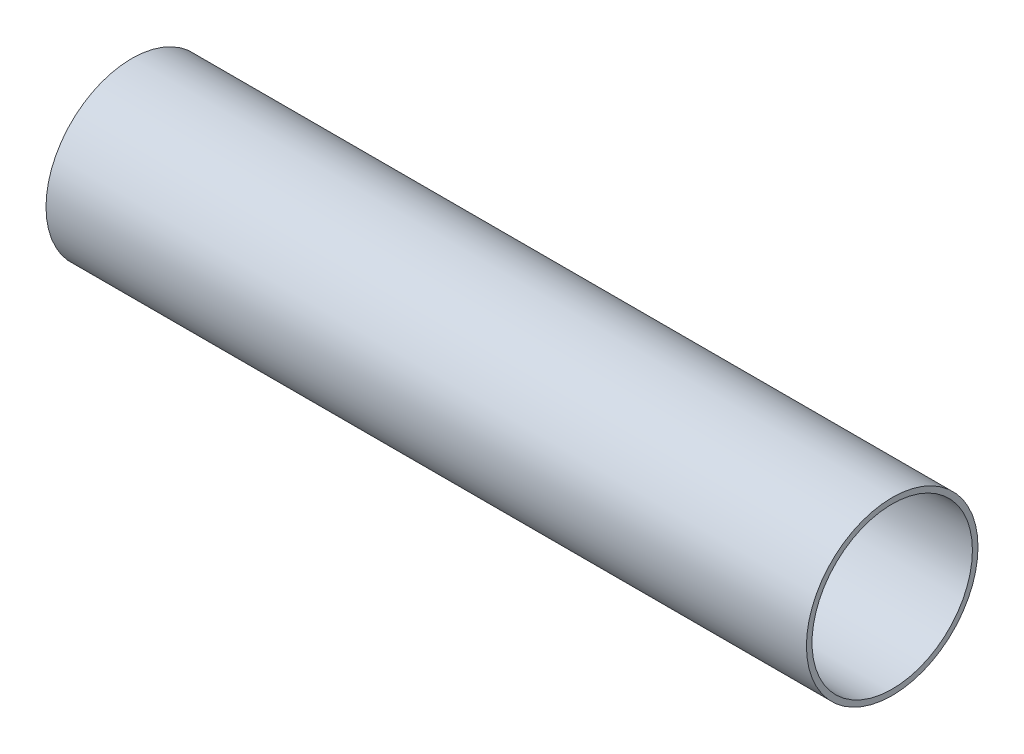
SolidWorks part; units mm, degrees
ref_plane "Front Plane" through (0, 0, 0) normal (0, 0, 1) x (1, 0, 0)
ref_plane "Top Plane" through (0, 0, 0) normal (0, 1, 0) x (1, 0, 0)
ref_plane "Right Plane" through (0, 0, 0) normal (1, 0, 0) x (0, 0, -1)
sketch "Sketch1" plane through (0, 0, 0) normal (1, 0, 0) x (0, 0, -1)
  circle A0 centre (0, 0) radius 45.847
  circle A1 centre (0, 0) radius 42.8625
  dimension "D1" = 91.694
  dimension "D2" = 85.725
extrude "Boss-Extrude1" add sketch "Sketch1" along normal blind 406.4
